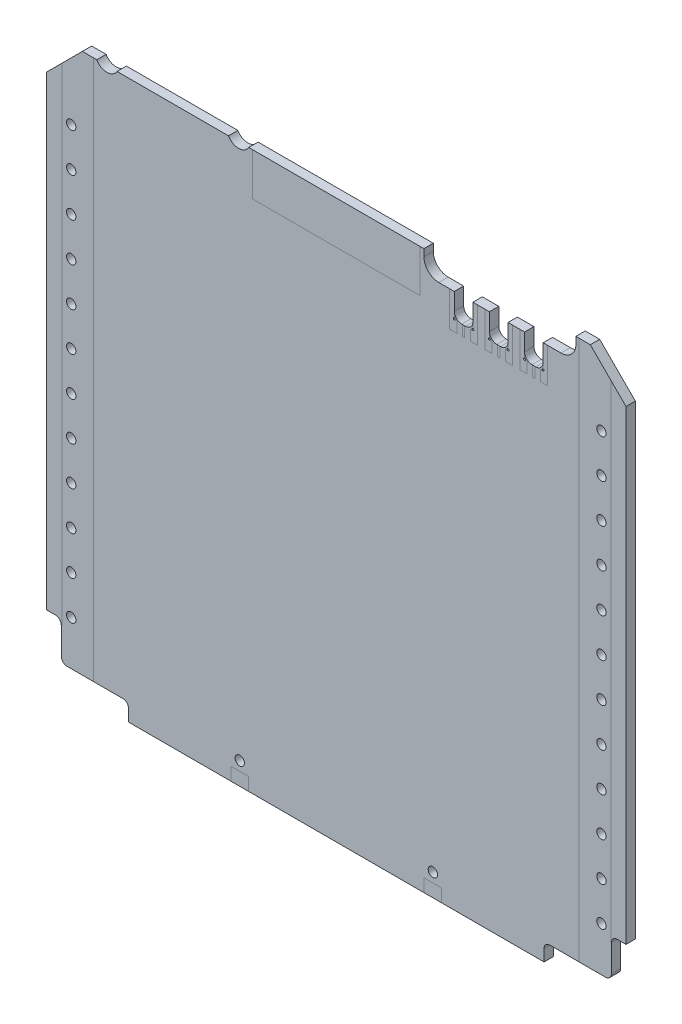
SolidWorks part; units mm, degrees
material "FR4_stuffedProtoboard"
ref_plane "Front Plane" through (0, 0, 0) normal (0, 0, 1) x (1, 0, 0)
ref_plane "Top Plane" through (0, 0, 0) normal (0, 1, 0) x (1, 0, 0)
ref_plane "Right Plane" through (0, 0, 0) normal (1, 0, 0) x (0, 0, -1)
ref_plane "Plane4" through (0, 0, -0.0125) normal (0, 0, -1) x (-1, 0, 0)
sketch "Sketch1" plane through (0, 0, -0.0125) normal (0, 0, -1) x (-1, 0, 0)
  line L4 (49.5, -50) -> (49.5, 45.3)
  line L6 (49.5, 45.3) -> (-49.5, 45.3)
  line L12 (-49.5, 45.3) -> (-49.5, -50)
  line L17 (-49.5, -50) -> (49.5, -50)
  line L18 (0, -50) -> (0, 45.3) construction
  dimension "D7" = 95.3
  dimension "D1" = 99
  dimension "D34" = 50
extrude "basicSize" add sketch "Sketch1" against normal blind 1.6
chamfer "Chamfer1" distance 6.1 angle 45 2 edges at (49.5, 45.3, 0.7875) (-49.5, 45.3, 0.7875)
sketch "Sketch4" plane through (0, 0, 1.5875) normal (0, 0, 1) x (1, 0, 0)
  line L1 (37.4679, 45.3) -> (40.9321, 45.3)
  line L7 (-43.4, 45.3) -> (43.4, 45.3) construction
  line L8 (49.5, 39.2) -> (49.5, -50) construction
  arc A0 (40.9321, 45.3) -> (37.4679, 45.3) centre (39.2, 46.3) cw
  point P5 (39.2, 44.3)
  dimension "D1" = 2
  dimension "D3" = 10.3
  dimension "D2" = 1
extrude "backplaneSideScrewCutout" cut sketch "Sketch4" against normal through all both and the other way through all
pattern_linear "LPattern3" count 2 spacing 22.5 along (-1, 0, 0) of "backplaneSideScrewCutout"
mirror "Mirror3" about plane through (0, 0, 0) normal (1, 0, 0) of "LPattern3"
sketch "Sketch6" plane through (0, 0, 1.5875) normal (0, 0, 1) x (1, 0, 0)
  line L0 (-49.5, -50) -> (-49.5, 39.2) construction
  line L1 (-49.5, -40.4) -> (-47, -40.4)
  line L2 (-49.5, -40.4) -> (-49.5, -50)
  line L4 (-47, -40.4) -> (-47, -47)
  line L5 (49.5, -50) -> (-49.5, -50) construction
  line L6 (-35.5, -50) -> (-49.5, -50)
  line L7 (-35.5, -50) -> (-35.5, -47)
  line L8 (-35.5, -47) -> (-47, -47)
  dimension "D1" = 2.5
  dimension "D2" = 3
  dimension "D3" = 9.6
  dimension "D4" = 14
extrude "Cut-Extrude4" cut sketch "Sketch6" against normal through all
fillet "Fillet1" radius 1 3 edges at (-35.5, -47, 0.7875) (-47, -47, 0.7875) (-47, -40.4, 0.7875)
mirror "Mirror1" about plane through (0, 0, 0) normal (1, 0, 0) of "Cut-Extrude4", "Fillet1"
sketch "Sketch7" plane through (0, 0, 1.5875) normal (0, 0, 1) x (1, 0, 0)
  line L0 (-14.2875, 45.5) -> (-14.2875, 39.912) construction
  line L1 (-14.2875, 45.3) -> (-14.2875, 38.007)
  line L2 (-12.2428, 38.007) -> (-11.8872, 38.007) construction
  line L3 (-14.2875, 38.007) -> (14.2875, 38.007)
  line L4 (14.2875, 45.5) -> (14.2875, 39.912) construction
  line L5 (14.2875, 45.3) -> (14.2875, 38.007)
  line L7 (-14.9679, 45.3) -> (14.9679, 45.3) construction
  line L8 (-14.2875, 45.3) -> (14.2875, 45.3)
extrude "TigerEyeFootprint" cut sketch "Sketch7" against normal blind 0.0001
sketch "thermalContacts_upper" plane through (0, 0, 1.5875) normal (0, 0, 1) x (1, 0, 0)
  line L0 (-49.5, -40.4) -> (-49.5, 39.2) construction
  line L1 (35.5, -50) -> (-35.5, -50) construction
  line L3 (-46.9, 45.3) -> (-46.9, -41.5)
  line L4 (-37.4679, 45.3) -> (-18.4321, 45.3) construction
  line L23 (-46.9, 45.3) -> (-56.3922, 45.3)
  line L24 (-56.3922, 45.3) -> (-56.3922, -41.5)
  line L25 (-56.3922, -41.5) -> (-46.9, -41.5)
  dimension "D1" = 2.6
  dimension "D2" = 8.5
extrude "keepOut_bottom" cut sketch "thermalContacts_upper" against normal blind 0.0001
sketch "Sketch3" plane through (0, 0, 1.5875) normal (0, 0, 1) x (1, 0, 0)
  line L1 (-47, -46) -> (-47, -41.5) construction
  line L2 (-36.5, -47) -> (-46, -47) construction
  line L3 (-14.9679, 45.3) -> (14.9679, 45.3) construction
  line L5 (-49.5, -40.4) -> (-49.5, 39.2) construction
  line L6 (-46.9, -41.5) -> (-46.9, 41.8) construction
  line L7 (-46.9, -41.5) -> (-47, -41.5)
  line L8 (-47, -46) -> (-47, -41.5) construction
  line L9 (-47, -41.5) -> (-46.9, -41.5) construction
  line L10 (0, -50) -> (0, 45.3) construction
  line L11 (35.5, -50) -> (-35.5, -50) construction
  line L12 (-43.4, 45.3) -> (-40.9321, 45.3) construction
  line L13 (-41.5, 45.3) -> (-46.9, 45.3)
  line L14 (-46, -47) -> (-41.5, -47)
  line L15 (-47, -41.5) -> (-47, -46)
  line L16 (-46.9, 45.3) -> (-46.9, -41.5)
  line L17 (-41.5, -47) -> (-41.5, 45.3)
  arc A3 (-47, -46) -> (-46, -47) centre (-46, -46) ccw construction
  arc A4 (-46, -47) -> (-47, -46) centre (-46, -46) cw
  dimension "D1" = 8
extrude "caution_top" cut sketch "Sketch3" against normal blind 0.0001
sketch "hold-downLocations" plane through (0, 0, 1.5875) normal (0, 0, 1) x (1, 0, 0)
  line L1 (-18, -47.8) -> (-15, -47.8) construction
  line L3 (15, -47.8) -> (18, -47.8)
  line L4 (18, -47.8) -> (18, -50)
  line L5 (35.5, -50) -> (-35.5, -50) construction
  line L6 (18, -50) -> (15, -50)
  line L7 (15, -50) -> (15, -47.8)
  line L8 (-15, -47.8) -> (-15, -50) construction
  line L9 (-15, -50) -> (-18, -50) construction
  line L10 (-18, -50) -> (-18, -47.8) construction
  line L11 (0, -50) -> (0, -47.8) construction
  line L12 (-15, -47.8) -> (15, -47.8) construction
  dimension "D1" = 3
  dimension "D2" = 2.2
  dimension "D3" = 3
  dimension "D5" = 30
extrude "hold-downFootprints" cut sketch "hold-downLocations" against normal blind 0.0001
ref_plane "midplane_Z" through (0, 0, 0.7875) normal (0, 0, 1) x (1, 0, 0)
mirror "clearances_top-bottom" about plane through (0, 0, 0.7875) normal (0, 0, 1) of "hold-downFootprints", "caution_top", "keepOut_bottom"
mirror "clearances_side-side" about plane through (0, 0, 0) normal (1, 0, 0) of "clearances_top-bottom"
sketch "Sketch10" plane through (0, 0, -0.0125) normal (0, 0, -1) x (-1, 0, 0)
  line L0 (-15, -47.8) -> (-15, -50) construction
  line L1 (-18, -47.8) -> (-15, -47.8)
  line L2 (-18, -47.8) -> (-18, -44.5)
  line L3 (-18, -44.5) -> (-15, -44.5)
  line L4 (-15, -47.8) -> (-15, -44.5)
  line L5 (-15, -50) -> (15, -50) construction
  line L6 (0, -50) -> (0, -41.5199) construction
  line L7 (15, -47.8) -> (15, -44.5)
  line L8 (18, -44.5) -> (15, -44.5)
  line L9 (18, -47.8) -> (18, -44.5)
  line L10 (18, -47.8) -> (15, -47.8)
  dimension "D1" = 5.5
extrude "bottomsideShelfKeepouts" cut sketch "Sketch10" against normal up to surface (0.0001 mm away) up to face at (16.5, -48.9, -0.0124)
sketch "recommendedBuildArea" [suppressed] plane through (0, 0, 1.5875) normal (0, 0, 1) x (1, 0, 0)
  line L0 (51.1146, 38.007) -> (51.1146, 56.8216) construction
  line L1 (-35.5, -45.5) -> (-46.8, -45.5) construction
  line L2 (-35.5, -47) -> (-35.5, -45.5) construction
  line L3 (35.5, -47) -> (35.5, -45.5) construction
  line L4 (14.2875, 45.3) -> (-14.2875, 45.3)
  line L5 (-14.2875, 45.3) -> (-14.2875, 38.007)
  line L6 (-14.2875, 38.007) -> (14.2875, 38.007)
  line L7 (-46.8, 41.9) -> (-49.5, 39.2)
  line L8 (-49.5, 39.2) -> (-49.5, -40.4)
  line L9 (-49.5, -40.4) -> (-48, -40.4)
  line L10 (-46.8, -41.5) -> (-46.8, 41.9)
  line L11 (-47, -41.4) -> (-47, -41.5)
  line L12 (-47, -41.4) -> (-47, -41.5)
  line L13 (-47, -41.5) -> (-46.8, -41.5)
  line L14 (35.5, -45.5) -> (46.8, -45.5) construction
  line L15 (54.1146, 35.007) -> (54.1146, 77.997)
  line L16 (54.1146, 77.997) -> (43.8, 42.325)
  line L17 (-46.8, -45.5) -> (-46.8, 41.9) construction
  line L20 (43.8, 42.325) -> (43.8, -42.5)
  line L21 (14.2875, 38.007) -> (14.2875, 45.3)
  line L22 (32.5, -42.5) -> (43.8, -42.5)
  line L23 (-14.2875, 45.3) -> (-14.2875, 38.007)
  line L24 (-14.2875, 38.007) -> (51.1146, 38.007)
  line L25 (32.5, -47) -> (32.5, -42.5)
  line L26 (32.5, -47) -> (32.5, -47)
  line L27 (21, -47) -> (32.5, -47)
  line L28 (21, -45) -> (21, -47)
  line L29 (46.8, -41.5) -> (47, -41.5)
  line L30 (46.8, -41.5) -> (47, -41.5)
  line L31 (46.8, 41.9) -> (46.8, -41.5)
  line L32 (48, -40.4) -> (49.5, -40.4)
  line L33 (49.5, -40.4) -> (49.5, 39.2)
  line L34 (49.5, 39.2) -> (46.8, 41.9)
  line L35 (47, -41.5) -> (47, -41.4)
  line L36 (12, -45) -> (21, -45)
  line L37 (47, -41.5) -> (47, -41.4)
  line L38 (46.8, 41.9) -> (46.8, -45.5) construction
  line L39 (12, -47) -> (12, -45)
  line L40 (-12, -47) -> (12, -47)
  line L41 (-12, -45) -> (-12, -47)
  line L42 (-21, -45) -> (-12, -45)
  line L43 (-21, -47) -> (-21, -45)
  line L44 (-32.5, -47) -> (-21, -47)
  line L45 (-32.5, -47) -> (-32.5, -47)
  line L46 (-32.5, -47) -> (-32.5, -42.5)
  line L47 (-32.5, -42.5) -> (-43.8, -42.5)
  line L48 (-43.8, -42.5) -> (-43.8, 34.7661)
  line L49 (-43.8, 34.7661) -> (-43.8, 34.7661)
  line L50 (-43.8, 34.7661) -> (-39.8793, 42.3)
  line L51 (-17.2875, 42.3) -> (-39.8793, 42.3)
  line L52 (-17.2875, 42.3) -> (-17.2875, 35.007)
  line L53 (-17.2875, 35.007) -> (54.1146, 35.007)
  line L59 (-47, -41.5) -> (-46.8, -41.5)
  line L72 (-15, -48) -> (-15, -50)
  line L73 (-15, -50) -> (15, -50)
  line L74 (15, -50) -> (15, -48)
  line L75 (15, -48) -> (18, -48)
  line L76 (18, -48) -> (18, -50)
  line L77 (18, -50) -> (35.5, -50)
  line L78 (35.5, -50) -> (35.5, -48)
  line L79 (36.5, -47) -> (41.5, -47)
  line L80 (41.5, -47) -> (41.5, 45.3)
  line L81 (41.5, 45.3) -> (40.9321, 45.3)
  line L82 (37.4679, 45.3) -> (34.25, 45.3)
  line L83 (34.25, 45.3) -> (34.25, 38.35)
  line L84 (34.25, 38.35) -> (30.75, 38.35)
  line L85 (30.75, 38.35) -> (30.75, 45.3)
  line L86 (30.75, 45.3) -> (29.25, 45.3)
  line L87 (29.25, 45.3) -> (29.25, 38.35)
  line L88 (29.25, 38.35) -> (25.75, 38.35)
  line L89 (25.75, 38.35) -> (25.75, 45.3)
  line L90 (25.75, 45.3) -> (24.25, 45.3)
  line L91 (24.25, 45.3) -> (24.25, 38.35)
  line L92 (24.25, 38.35) -> (20.75, 38.35)
  line L93 (20.75, 38.35) -> (20.75, 45.3)
  line L94 (20.75, 45.3) -> (18.4321, 45.3)
  line L95 (14.9679, 45.3) -> (14.2875, 45.3)
  line L96 (14.2875, 45.3) -> (14.2875, 38.007)
  line L97 (14.2875, 38.007) -> (-14.2875, 38.007)
  line L98 (-14.2875, 38.007) -> (-14.2875, 45.3)
  line L99 (-14.2875, 45.3) -> (-14.9679, 45.3)
  line L100 (-18.4321, 45.3) -> (-37.4679, 45.3)
  line L101 (-40.9321, 45.3) -> (-41.5, 45.3)
  line L102 (41.5, -47) -> (41.5, 45.3)
  line L103 (-41.5, -47) -> (-36.5, -47)
  line L104 (-35.5, -48) -> (-35.5, -50)
  line L105 (-35.5, -50) -> (-18, -50)
  line L106 (-18, -50) -> (-18, -48)
  line L107 (-18, -48) -> (-15, -48)
  line L108 (-15, -48) -> (-15, -50) construction
  line L109 (-15, -50) -> (15, -50) construction
  line L110 (15, -50) -> (15, -48) construction
  line L111 (15, -48) -> (18, -48) construction
  line L112 (18, -48) -> (18, -50) construction
  line L113 (18, -50) -> (35.5, -50) construction
  line L114 (35.5, -50) -> (35.5, -47) construction
  line L115 (35.5, -47) -> (41.5, -47) construction
  line L133 (51.1146, 38.007) -> (-14.2875, 38.007)
  line L134 (-14.2875, 38.007) -> (-14.2875, 45.3)
  line L136 (-14.2875, 45.3) -> (-41.7, 45.3) construction
  line L139 (-41.5, -47) -> (-35.5, -47) construction
  line L140 (-35.5, -47) -> (-35.5, -50) construction
  line L141 (-35.5, -50) -> (-18, -50) construction
  line L142 (-18, -50) -> (-18, -48) construction
  line L143 (-18, -48) -> (-15, -48) construction
  line L144 (-46.8, 35.5) -> (-41.7, 45.3) construction
  line L160 (-41.5, 45.3) -> (-41.5, -47)
  line L161 (-41.5, 45.3) -> (-41.5, -47)
  line L162 (-46.8, 41.9) -> (-46.8, 35.5) construction
  line L163 (51.1146, 56.8216) -> (46.8, 41.9) construction
  arc A1 (-47, -41.4) -> (-48, -40.4) centre (-48, -41.4) ccw
  arc A3 (48, -40.4) -> (47, -41.4) centre (48, -41.4) ccw
  arc A10 (36.5, -47) -> (35.5, -48) centre (36.5, -48) ccw
  arc A11 (37.4679, 45.3) -> (40.9321, 45.3) centre (39.2, 46.3) ccw
  arc A12 (14.9679, 45.3) -> (18.4321, 45.3) centre (16.7, 46.3) ccw
  arc A13 (-18.4321, 45.3) -> (-14.9679, 45.3) centre (-16.7, 46.3) ccw
  arc A14 (-40.9321, 45.3) -> (-37.4679, 45.3) centre (-39.2, 46.3) ccw
  arc A15 (-35.5, -48) -> (-36.5, -47) centre (-36.5, -48) ccw
  dimension "D5" = 1.5
  dimension "D1" = 0
  dimension "D2" = 0
  dimension "D3" = 0
  dimension "D4" = 0
  dimension "D6" = 3
ref_point "rail midpoint"
sketch "locatorSketch" plane through (0, 0, 1.5875) normal (0, 0, 1) x (1, 0, 0)
  line L0 (-12.2428, 39.531) -> (12.2428, 38.007) construction
  line L1 (12.2428, 39.531) -> (-12.2428, 38.007) construction
  line L2 (-21.9628, 39.277) -> (-33.0372, 38.261) construction
  line L3 (-33.0372, 39.277) -> (-21.9628, 38.261) construction
  line L4 (-12.2428, 38.261) -> (-12.2428, 38.007)
  line L5 (-11.8872, 38.261) -> (-12.2428, 38.261)
  line L6 (-11.8872, 38.007) -> (-11.8872, 38.261)
  line L7 (-12.2428, 38.007) -> (-11.8872, 38.007)
  line L8 (-12.2428, 38.261) -> (-12.2428, 38.007)
  line L9 (-11.8872, 38.261) -> (-12.2428, 38.261)
  line L10 (-11.8872, 38.007) -> (-11.8872, 38.261)
  line L11 (-12.2428, 38.007) -> (-11.8872, 38.007)
  line L12 (-12.2428, 39.531) -> (-12.2428, 39.277)
  line L13 (-11.8872, 39.531) -> (-12.2428, 39.531)
  line L14 (-11.8872, 39.277) -> (-11.8872, 39.531)
  line L15 (-12.2428, 39.277) -> (-11.8872, 39.277)
  line L16 (-12.2428, 39.531) -> (-12.2428, 39.277)
  line L17 (-11.8872, 39.531) -> (-12.2428, 39.531)
  line L18 (-11.8872, 39.277) -> (-11.8872, 39.531)
  line L19 (-12.2428, 39.277) -> (-11.8872, 39.277)
  line L20 (11.8872, 39.531) -> (11.8872, 39.277)
  line L21 (12.2428, 39.531) -> (11.8872, 39.531)
  line L22 (12.2428, 39.277) -> (12.2428, 39.531)
  line L23 (11.8872, 39.277) -> (12.2428, 39.277)
  line L24 (11.8872, 39.531) -> (11.8872, 39.277)
  line L25 (12.2428, 39.531) -> (11.8872, 39.531)
  line L26 (12.2428, 39.277) -> (12.2428, 39.531)
  line L27 (11.8872, 39.277) -> (12.2428, 39.277)
  line L28 (11.8872, 38.261) -> (11.8872, 38.007)
  line L29 (12.2428, 38.261) -> (11.8872, 38.261)
  line L30 (12.2428, 38.007) -> (12.2428, 38.261)
  line L31 (11.8872, 38.007) -> (12.2428, 38.007)
  line L32 (11.8872, 38.261) -> (11.8872, 38.007)
  line L33 (12.2428, 38.261) -> (11.8872, 38.261)
  line L34 (12.2428, 38.007) -> (12.2428, 38.261)
  line L35 (11.8872, 38.007) -> (12.2428, 38.007)
  line L38 (-21.9628, 39.531) -> (-21.9628, 39.277)
  line L39 (-21.6072, 39.531) -> (-21.9628, 39.531)
  line L40 (-21.6072, 39.277) -> (-21.6072, 39.531)
  line L41 (-21.9628, 39.277) -> (-21.6072, 39.277)
  line L42 (-21.9628, 39.531) -> (-21.9628, 39.277)
  line L43 (-21.6072, 39.531) -> (-21.9628, 39.531)
  line L44 (-21.6072, 39.277) -> (-21.6072, 39.531)
  line L45 (-21.9628, 39.277) -> (-21.6072, 39.277)
  line L46 (-33.3928, 38.261) -> (-33.3928, 38.007)
  line L47 (-33.0372, 38.261) -> (-33.3928, 38.261)
  line L48 (-33.0372, 38.007) -> (-33.0372, 38.261)
  line L49 (-33.3928, 38.007) -> (-33.0372, 38.007)
  line L50 (-33.3928, 38.261) -> (-33.3928, 38.007)
  line L51 (-33.0372, 38.261) -> (-33.3928, 38.261)
  line L52 (-33.0372, 38.007) -> (-33.0372, 38.261)
  line L53 (-33.3928, 38.007) -> (-33.0372, 38.007)
  line L55 (-21.9628, 38.261) -> (-21.9628, 38.007)
  line L56 (-21.6072, 38.261) -> (-21.9628, 38.261)
  line L57 (-21.6072, 38.007) -> (-21.6072, 38.261)
  line L58 (-21.9628, 38.007) -> (-21.6072, 38.007)
  line L59 (-21.9628, 38.261) -> (-21.9628, 38.007)
  line L60 (-21.6072, 38.261) -> (-21.9628, 38.261)
  line L61 (-21.6072, 38.007) -> (-21.6072, 38.261)
  line L62 (-21.9628, 38.007) -> (-21.6072, 38.007)
  line L63 (-33.3928, 39.531) -> (-33.3928, 39.277)
  line L64 (-33.0372, 39.531) -> (-33.3928, 39.531)
  line L65 (-33.0372, 39.277) -> (-33.0372, 39.531)
  line L66 (-33.3928, 39.277) -> (-33.0372, 39.277)
  line L67 (-33.3928, 39.531) -> (-33.3928, 39.277)
  line L68 (-33.0372, 39.531) -> (-33.3928, 39.531)
  line L69 (-33.0372, 39.277) -> (-33.0372, 39.531)
  line L70 (-33.3928, 39.277) -> (-33.0372, 39.277)
  dimension "D1" = 0
  dimension "D2" = 0
  dimension "D3" = 0
  dimension "D4" = 0
  dimension "D5" = 0
  dimension "D6" = 0
  dimension "D7" = 0
  dimension "D8" = 0
sketch "Sketch8" plane through (0, 0, 1.5875) normal (0, 0, 1) x (1, 0, 0)
  line L0 (-49.5, -40.4) -> (-48, -40.4) construction
  line L2 (-49.5, -40.4) -> (-49.5, 39.2) construction
  line L3 (-41.5, 45.3) -> (-43.4, 45.3) construction
  line L4 (-18, -47.8) -> (-15, -47.8) construction
  line L5 (-45.3, 33.5) -> (-46.9, 33.5) construction
  line L6 (-46.9, 41.8) -> (-46.9, -41.5) construction
  line L7 (-16.5, -46.2) -> (-16.5, -47.8) construction
  line L8 (-18, -47.8) -> (-15, -47.8) construction
  circle A0 centre (-45.3, 33.5) radius 0.8
  circle A1 centre (-45.3, 26.8727) radius 0.8
  circle A2 centre (-45.3, 20.2455) radius 0.8
  circle A3 centre (-45.3, 13.6182) radius 0.8
  circle A4 centre (-45.3, 6.9909) radius 0.8
  circle A5 centre (-45.3, 0.3636) radius 0.8
  circle A6 centre (-45.3, -6.2636) radius 0.8
  circle A7 centre (-45.3, -12.8909) radius 0.8
  circle A8 centre (-45.3, -19.5182) radius 0.8
  circle A9 centre (-45.3, -26.1455) radius 0.8
  circle A10 centre (-45.3, -32.7727) radius 0.8
  circle A11 centre (-45.3, -39.4) radius 0.8
  circle A12 centre (-16.5, -46.2) radius 0.8
  point P35 (-16.5, -47.8)
  dimension "D1" = 1.6
  dimension "D3" = 1
  dimension "D5" = 4.2
  dimension "D6" = 11.8
  dimension "D2" = 12
extrude "springPinHoleSeed" cut sketch "Sketch8" against normal blind 10
mirror "Mirror4" about plane through (0, 0, 0) normal (1, 0, 0) of "springPinHoleSeed"
sketch "Sketch9" plane through (0, 0, 1.5875) normal (0, 0, 1) x (1, 0, 0)
  circle A0 centre (-45.3, 33.5) radius 1.35
  dimension "D1" = 2.7
sketch "bottomsideKeepout_trace" plane through (0, 0, -0.0125) normal (0, 0, -1) x (-1, 0, 0)
  line L0 (18, -50) -> (18, -44.5) construction
  line L1 (18, -44.5) -> (15, -44.5) construction
  line L2 (15, -44.5) -> (15, -50) construction
  line L3 (-15, -44.5) -> (-15, -50) construction
  line L4 (-15, -44.5) -> (-18, -44.5) construction
  line L5 (-18, -50) -> (-18, -44.5) construction
  line L6 (18, -50) -> (18, -44.5)
  line L7 (18, -44.5) -> (15, -44.5)
  line L8 (15, -44.5) -> (15, -50)
  line L9 (-15, -44.5) -> (-15, -50)
  line L10 (-15, -44.5) -> (-18, -44.5)
  line L11 (-18, -50) -> (-18, -44.5)
  line L12 (15, -50) -> (18, -50) construction
  line L13 (-15, -50) -> (-18, -50) construction
  line L14 (15, -50) -> (18, -50)
  line L15 (-15, -50) -> (-18, -50)
sketch "Sketch11" plane through (0, 0, 1.5875) normal (0, 0, 1) x (1, 0, 0)
  line L0 (49.5, 39.2) -> (49.5, -40.4) construction
  line L6 (35.34, 41.56) -> (32.16, 41.56)
  line L8 (35.34, 41.56) -> (35.34, 37.36)
  line L11 (35.34, 37.36) -> (32.16, 37.36)
  line L12 (32.16, 41.56) -> (32.16, 37.36)
  line L13 (35.34, 41.56) -> (32.16, 37.36) construction
  line L14 (35.34, 37.36) -> (32.16, 41.56) construction
  line L18 (29.34, 41.56) -> (26.16, 41.56)
  line L19 (29.34, 41.56) -> (29.34, 37.36)
  line L20 (29.34, 37.36) -> (26.16, 37.36)
  line L21 (26.16, 41.56) -> (26.16, 37.36)
  line L22 (29.34, 41.56) -> (26.16, 37.36) construction
  line L23 (29.34, 37.36) -> (26.16, 41.56) construction
  line L24 (23.34, 41.56) -> (20.16, 41.56)
  line L25 (23.34, 41.56) -> (23.34, 37.36)
  line L26 (23.34, 37.36) -> (20.16, 37.36)
  line L27 (20.16, 41.56) -> (20.16, 37.36)
  line L28 (23.34, 41.56) -> (20.16, 37.36) construction
  line L29 (23.34, 37.36) -> (20.16, 41.56) construction
  line L30 (18.4321, 45.3) -> (37.4679, 45.3) construction
  line L31 (16.7, 46.3) -> (39.2, 46.3) construction
  point P4 (33.75, 39.46)
  point P10 (27.95, 46.3)
  point P15 (27.75, 39.46)
  point P20 (21.75, 39.46)
  dimension "D5" = 6
  dimension "D1" = 3.18
  dimension "D2" = 4.2
  dimension "D3" = 21.75
  dimension "D4" = 3
  dimension "D6" = 3.74
extrude "Cut-Extrude5" cut sketch "Sketch11" against normal blind 10
fillet "Fillet2" radius 1.27 6 edges at (23.34, 37.36, 0.7875) (29.34, 37.36, 0.7875) (35.34, 37.36, 0.7875) (32.16, 37.36, 0.7875) (26.16, 37.36, 0.7875) (20.16, 37.36, 0.7875)
hole_wizard "Ø0.32 (0.32) Diameter Hole1" positions "Sketch12" profile "Sketch13" hole size "Ø0.32" standard "ANSI Metric"
sketch "Sketch12" plane through (0, 0, 1.5875) normal (0, 0, 1) x (1, 0, 0)
  line L1 (35.34, 38.63) -> (35.34, 41.56) construction
  line L2 (32.16, 41.56) -> (32.16, 38.63) construction
  line L3 (33.75, 37.36) -> (34.7997, 37.36) construction
  line L4 (33.43, 37.36) -> (34.07, 37.36) construction
  point P0 (35.34, 37.52)
  point P2 (32.16, 37.52)
  point P16 (29.34, 37.52)
  point P17 (26.16, 37.52)
  point P18 (23.34, 37.52)
  point P19 (20.16, 37.52)
  dimension "D2" = 6
  dimension "D3" = 0.16
  dimension "D1" = 3
sketch "Sketch13" plane through (35.34, 37.52, 1.5875) normal (1, 0, 0) x (0, -1, 0)
  line L0 (0, 0) -> (0, 9.6211)
  line L1 (0, 9.6211) -> (0.16, 9.525)
  line L2 (0.16, 9.525) -> (0.16, 0)
  line L5 (0.16, 0) -> (0, 0)
  line L10 (0, 9.6211) -> (-0.16, 9.525) construction
  line L11 (0, -6.35) -> (0, 107.95) construction
  dimension "Hole Dia." = 0.32
  dimension "Hole Depth" = 9.525
  dimension "Drill Angle" = 118
sketch "Sketch14" plane through (0, 0, 1.5875) normal (0, 0, 1) x (1, 0, 0)
  line L1 (36.125, 41.56) -> (35.34, 41.56)
  line L2 (36.125, 41.56) -> (36.125, 35.57)
  line L3 (36.125, 35.57) -> (34.895, 35.57)
  line L4 (31.375, 41.56) -> (31.375, 35.57)
  line L5 (36.125, 41.56) -> (31.375, 35.57) construction
  line L6 (36.125, 35.57) -> (31.375, 41.56) construction
  line L7 (33.75, 37.36) -> (33.75, 35.57) construction
  line L8 (33.43, 37.36) -> (34.07, 37.36) construction
  line L9 (32.605, 35.57) -> (32.605, 37.36)
  line L10 (33.56, 37.36) -> (33.94, 37.36)
  line L11 (33.56, 37.36) -> (33.56, 35.57)
  line L12 (33.56, 35.57) -> (33.94, 35.57)
  line L13 (33.94, 37.36) -> (33.94, 35.57)
  line L14 (33.56, 37.36) -> (33.94, 35.57) construction
  line L15 (33.56, 35.57) -> (33.94, 37.36) construction
  line L16 (34.895, 35.57) -> (34.895, 37.36)
  line L17 (33.94, 35.57) -> (33.56, 35.57)
  line L18 (32.16, 41.56) -> (32.16, 38.63) construction
  line L19 (35.34, 38.63) -> (35.34, 41.56) construction
  line L20 (32.16, 41.56) -> (32.16, 38.63)
  line L21 (35.34, 38.63) -> (35.34, 41.56)
  line L22 (33.56, 37.36) -> (33.94, 37.36)
  line L23 (32.16, 41.56) -> (31.375, 41.56)
  line L24 (32.605, 37.36) -> (32.16, 37.36)
  line L25 (34.895, 37.36) -> (35.34, 37.36)
  line L26 (32.16, 37.68) -> (32.16, 38.63)
  line L27 (35.34, 37.68) -> (35.34, 38.63)
  line L28 (32.605, 35.57) -> (31.375, 35.57)
  circle A2 centre (32.16, 37.52) radius 0.16 construction
  circle A3 centre (35.34, 37.52) radius 0.16 construction
  arc A6 (32.16, 37.68) -> (32.16, 37.36) centre (32.16, 37.52) ccw
  arc A7 (35.34, 37.36) -> (35.34, 37.68) centre (35.34, 37.52) ccw
  point P4 (33.75, 38.565)
  point P15 (33.75, 36.465)
  dimension "D1" = 5.99
  dimension "D2" = 4.75
  dimension "D3" = 2.29
  dimension "D4" = 0.38
extrude "Boss-Extrude1" add sketch "Sketch14" along normal blind 0.0001 contours A6 L26 L20 L23 L4 L28 L9 L24 | L13 L10 L11 L12 | A7 L25 L16 L3 L2 L1 L21 L27 region at (35.6451, 38.2662, 1.5875) region at (31.8549, 38.2662, 1.5875) region at (33.75, 36.465, 1.5875)
pattern_linear "LPattern4" count 3 spacing 6 along (-1, 0, 0) of "Boss-Extrude1"
sketch "Sketch15" plane through (0, 0, 1.5875) normal (0, 0, 1) x (1, 0, 0)
  line L0 (18.4321, 45.3) -> (37.4679, 45.3) construction
  line L1 (14.9679, 45.3) -> (40.9321, 45.3)
  line L2 (14.9679, 45.3) -> (14.9679, 44.1)
  line L3 (17.5079, 41.56) -> (38.3921, 41.56)
  line L4 (40.9321, 45.3) -> (40.9321, 44.1)
  line L5 (14.9679, 45.3) -> (40.9321, 41.56) construction
  line L6 (14.9679, 41.56) -> (40.9321, 45.3) construction
  line L7 (35.34, 41.56) -> (32.16, 41.56) construction
  arc A0 (38.3921, 41.56) -> (40.9321, 44.1) centre (38.3921, 44.1) ccw
  arc A1 (14.9679, 44.1) -> (17.5079, 41.56) centre (17.5079, 44.1) ccw
  arc A2 (14.9679, 45.3) -> (18.4321, 45.3) centre (16.7, 46.3) ccw construction
  point P4 (27.95, 43.43)
  dimension "D3" = 2.54
extrude "Cut-Extrude6" cut sketch "Sketch15" against normal through all and the other way through all
